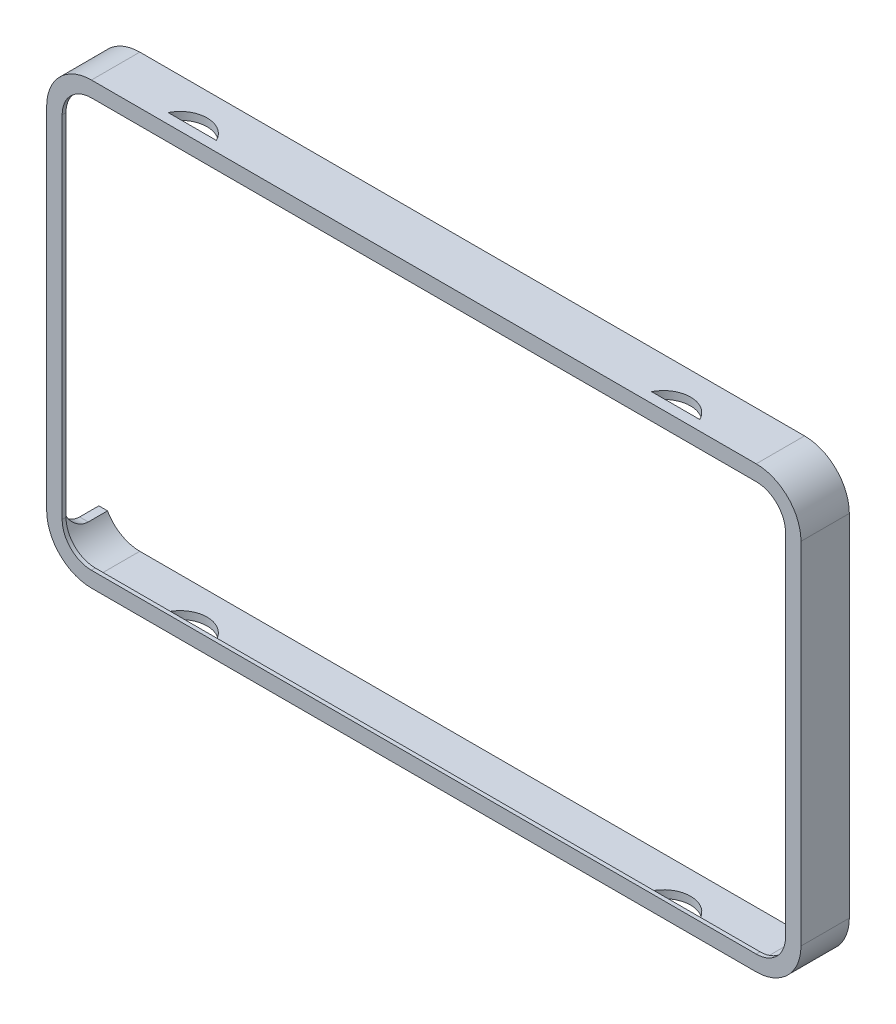
SolidWorks part; units mm, degrees
material "ABS"
ref_plane "Front" through (0, 0, 0) normal (0, 0, 1) x (1, 0, 0)
ref_plane "Top" through (0, 0, 0) normal (0, 1, 0) x (1, 0, 0)
ref_plane "Right" through (0, 0, 0) normal (1, 0, 0) x (0, 0, -1)
ref_axis "Axis1" through (0, 0, 0.635) along (0, 0, -1)
sketch "Sketch1" plane through (0, 0, 0) normal (0, 0, 1) x (1, 0, 0)
  line L0 (-87.3125, -55.5625) -> (87.3125, -55.5625) construction
  line L1 (96.8375, -46.0375) -> (96.8375, 46.0375) construction
  line L2 (87.3125, 55.5625) -> (-87.3125, 55.5625) construction
  line L3 (-96.8375, 46.0375) -> (-96.8375, -46.0375) construction
  line L4 (87.3125, 55.7657) -> (-87.3125, 55.7657)
  line L5 (-97.0407, 46.0375) -> (-97.0407, -46.0375)
  line L6 (-87.3125, -55.7657) -> (87.3125, -55.7657)
  line L7 (97.0407, -46.0375) -> (97.0407, 46.0375)
  line L8 (-99.0727, 46.0375) -> (-99.0727, -46.0375)
  line L9 (-87.3125, -57.7977) -> (87.3125, -57.7977)
  line L10 (99.0727, -46.0375) -> (99.0727, 46.0375)
  line L11 (87.3125, 57.7977) -> (-87.3125, 57.7977)
  arc A0 (-96.8375, -46.0375) -> (-87.3125, -55.5625) centre (-87.3125, -46.0375) ccw construction
  arc A1 (87.3125, -55.5625) -> (96.8375, -46.0375) centre (87.3125, -46.0375) ccw construction
  arc A2 (96.8375, 46.0375) -> (87.3125, 55.5625) centre (87.3125, 46.0375) ccw construction
  arc A3 (-87.3125, 55.5625) -> (-96.8375, 46.0375) centre (-87.3125, 46.0375) ccw construction
  arc A4 (-87.3125, 55.7657) -> (-97.0407, 46.0375) centre (-87.3125, 46.0375) ccw
  arc A5 (-97.0407, -46.0375) -> (-87.3125, -55.7657) centre (-87.3125, -46.0375) ccw
  arc A6 (87.3125, -55.7657) -> (97.0407, -46.0375) centre (87.3125, -46.0375) ccw
  arc A7 (97.0407, 46.0375) -> (87.3125, 55.7657) centre (87.3125, 46.0375) ccw
  arc A8 (-87.3125, 57.7977) -> (-99.0727, 46.0375) centre (-87.3125, 46.0375) ccw
  arc A9 (-99.0727, -46.0375) -> (-87.3125, -57.7977) centre (-87.3125, -46.0375) ccw
  arc A10 (87.3125, -57.7977) -> (99.0727, -46.0375) centre (87.3125, -46.0375) ccw
  arc A11 (99.0727, 46.0375) -> (87.3125, 57.7977) centre (87.3125, 46.0375) ccw
  dimension "D3" = 9.525
  dimension "D4" = 96.8375
  dimension "D5" = 96.8375
  dimension "D6" = 55.5625
  dimension "D7" = 55.5625
  dimension "D1" = 0.2032
  dimension "D2" = 2.032
extrude "Boss-Extrude1" add sketch "Sketch1" against normal blind 12.7
sketch "Sketch5" plane through (0, 0, -12.7) normal (0, 0, -1) x (-1, 0, 0)
  line L0 (97.0407, 46.0375) -> (97.0407, -46.0375) construction
  line L1 (-87.3125, 55.7657) -> (87.3125, 55.7657) construction
  line L2 (-97.0407, -46.0375) -> (-97.0407, 46.0375) construction
  line L3 (87.3125, -55.7657) -> (-87.3125, -55.7657) construction
  line L4 (97.0407, 46.0375) -> (97.0407, -46.0375)
  line L5 (-87.3125, 55.7657) -> (87.3125, 55.7657)
  line L6 (-97.0407, -46.0375) -> (-97.0407, 46.0375)
  line L7 (87.3125, -55.7657) -> (-87.3125, -55.7657)
  arc A0 (97.0407, 46.0375) -> (87.3125, 55.7657) centre (87.3125, 46.0375) ccw construction
  arc A1 (-87.3125, 55.7657) -> (-97.0407, 46.0375) centre (-87.3125, 46.0375) ccw construction
  arc A2 (-97.0407, -46.0375) -> (-87.3125, -55.7657) centre (-87.3125, -46.0375) ccw construction
  arc A3 (87.3125, -55.7657) -> (97.0407, -46.0375) centre (87.3125, -46.0375) ccw construction
  arc A4 (97.0407, 46.0375) -> (87.3125, 55.7657) centre (87.3125, 46.0375) ccw
  arc A5 (-87.3125, 55.7657) -> (-97.0407, 46.0375) centre (-87.3125, 46.0375) ccw
  arc A6 (-97.0407, -46.0375) -> (-87.3125, -55.7657) centre (-87.3125, -46.0375) ccw
  arc A7 (87.3125, -55.7657) -> (97.0407, -46.0375) centre (87.3125, -46.0375) ccw
sketch "Sketch2" plane through (0, 0, 0) normal (0, 0, 1) x (1, 0, 0)
  line L16 (-97.0407, 46.0375) -> (-97.0407, -46.0375) construction
  line L17 (-87.3125, -55.7657) -> (87.3125, -55.7657) construction
  line L18 (97.0407, -46.0375) -> (97.0407, 46.0375) construction
  line L19 (87.3125, 55.7657) -> (-87.3125, 55.7657) construction
  line L20 (-95.0087, 46.0375) -> (-95.0087, -46.0375)
  line L21 (-87.3125, -53.7337) -> (87.3125, -53.7337)
  line L22 (95.0087, -46.0375) -> (95.0087, 46.0375)
  line L23 (87.3125, 53.7337) -> (-87.3125, 53.7337)
  line L24 (-95.0087, 46.0375) -> (-95.0087, -46.0375)
  line L25 (-87.3125, -53.7337) -> (87.3125, -53.7337)
  line L26 (95.0087, -46.0375) -> (95.0087, 46.0375)
  line L27 (87.3125, 53.7337) -> (-87.3125, 53.7337)
  line L28 (-97.0407, 46.0375) -> (-97.0407, -46.0375)
  line L29 (-87.3125, -55.7657) -> (87.3125, -55.7657)
  line L30 (97.0407, -46.0375) -> (97.0407, 46.0375)
  line L31 (87.3125, 55.7657) -> (-87.3125, 55.7657)
  arc A20 (-97.0407, -46.0375) -> (-87.3125, -55.7657) centre (-87.3125, -46.0375) ccw construction
  arc A21 (87.3125, -55.7657) -> (97.0407, -46.0375) centre (87.3125, -46.0375) ccw construction
  arc A22 (97.0407, 46.0375) -> (87.3125, 55.7657) centre (87.3125, 46.0375) ccw construction
  arc A23 (-87.3125, 55.7657) -> (-97.0407, 46.0375) centre (-87.3125, 46.0375) ccw construction
  arc A24 (-95.0087, -46.0375) -> (-87.3125, -53.7337) centre (-87.3125, -46.0375) ccw
  arc A25 (87.3125, -53.7337) -> (95.0087, -46.0375) centre (87.3125, -46.0375) ccw
  arc A26 (95.0087, 46.0375) -> (87.3125, 53.7337) centre (87.3125, 46.0375) ccw
  arc A27 (-87.3125, 53.7337) -> (-95.0087, 46.0375) centre (-87.3125, 46.0375) ccw
  arc A28 (-95.0087, -46.0375) -> (-87.3125, -53.7337) centre (-87.3125, -46.0375) ccw
  arc A29 (87.3125, -53.7337) -> (95.0087, -46.0375) centre (87.3125, -46.0375) ccw
  arc A30 (95.0087, 46.0375) -> (87.3125, 53.7337) centre (87.3125, 46.0375) ccw
  arc A31 (-87.3125, 53.7337) -> (-95.0087, 46.0375) centre (-87.3125, 46.0375) ccw
  arc A32 (-97.0407, -46.0375) -> (-87.3125, -55.7657) centre (-87.3125, -46.0375) ccw
  arc A33 (87.3125, -55.7657) -> (97.0407, -46.0375) centre (87.3125, -46.0375) ccw
  arc A34 (97.0407, 46.0375) -> (87.3125, 55.7657) centre (87.3125, 46.0375) ccw
  arc A35 (-87.3125, 55.7657) -> (-97.0407, 46.0375) centre (-87.3125, 46.0375) ccw
  dimension "D1" = 2.032
extrude "Boss-Extrude2" add sketch "Sketch2" against normal blind 1.016
sketch "Sketch3" plane through (-99.0727, 0, 0) normal (-1, 0, 0) x (0, 0, 1)
  line L0 (-12.7, 46.0375) -> (-12.7, -46.0375) construction
  line L1 (-12.7, 50.8) -> (-7.6374, 50.8)
  line L2 (-12.7, 50.8) -> (-12.7, -50.8)
  line L3 (-12.7, -50.8) -> (-7.6374, -50.8)
  line L4 (-2.5574, 45.72) -> (-2.5574, -45.72)
  line L5 (-12.7, 50.8) -> (-2.5574, -50.8) construction
  line L6 (-12.7, -50.8) -> (-2.5574, 50.8) construction
  line L7 (0, 0) -> (-16.6514, 0) construction
  line L8 (0, 46.0375) -> (0, -46.0375) construction
  arc A0 (-2.5574, -45.72) -> (-7.6374, -50.8) centre (-7.6374, -45.72) cw
  arc A1 (-2.5574, 45.72) -> (-7.6374, 50.8) centre (-7.6374, 45.72) ccw
  point P4 (-7.6287, 0)
  point P11 (-16.6514, 0)
  point P12 (-2.5574, 0)
  dimension "D3" = 5.08
  dimension "D1" = 101.6
  dimension "D2" = 10.1426
extrude "Cut-Extrude1" cut sketch "Sketch3" against normal up to next
sketch "Sketch4" plane through (0, 57.7977, 0) normal (0, 1, 0) x (1, 0, 0)
  line L0 (-87.3125, 2.667) -> (87.3125, 2.667) construction
  line L1 (-87.3125, 12.7) -> (-87.3125, 0) construction
  line L2 (87.3125, 12.7) -> (87.3125, 0) construction
  line L3 (0, 12.7) -> (0, 0) construction
  line L4 (87.3125, 12.7) -> (-87.3125, 12.7) construction
  line L5 (87.3125, 0) -> (-87.3125, 0) construction
  line L6 (-69.85, 2.667) -> (-57.15, 2.667)
  line L7 (69.85, 2.667) -> (57.15, 2.667)
  arc A0 (-69.85, 2.667) -> (-57.15, 2.667) centre (-63.5, -0.5358) cw
  arc A1 (69.85, 2.667) -> (57.15, 2.667) centre (63.5, -0.5358) ccw
  dimension "D3" = 7.112
  dimension "D1" = 2.667
  dimension "D2" = 12.7
  dimension "D4" = 57.15
extrude "Cut-Extrude2" cut sketch "Sketch4" against normal through all
